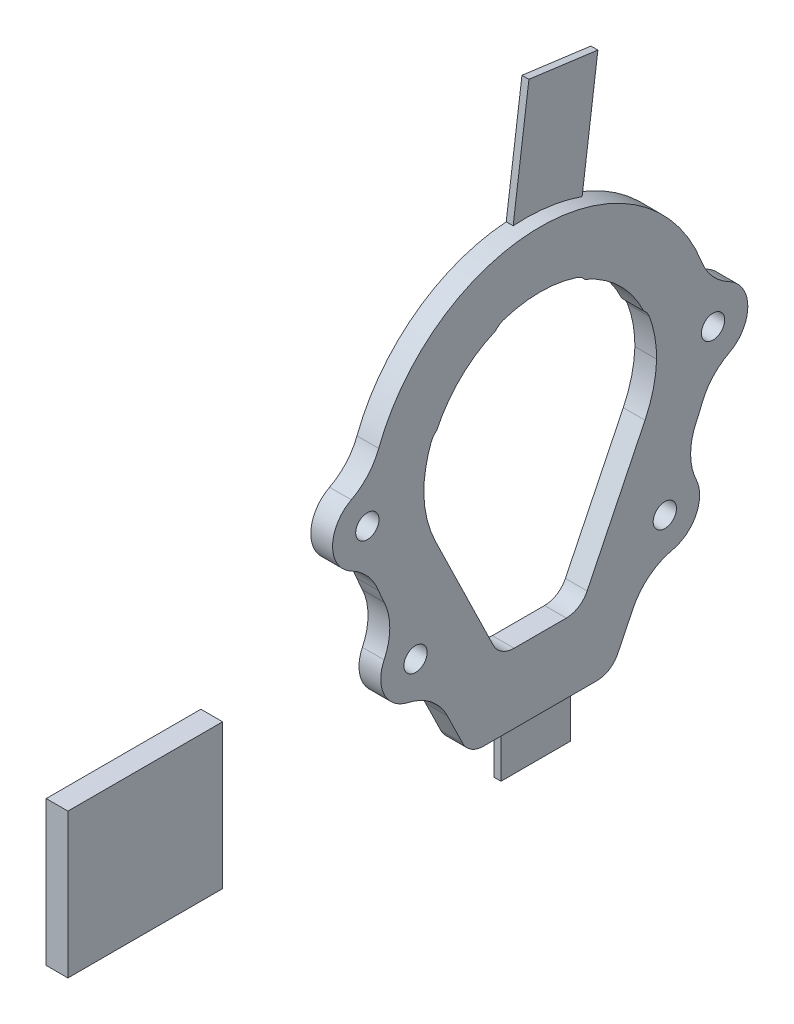
SolidWorks part; units mm, degrees
material "6061-T6 (SS)"
ref_plane "Front Plane" through (0, 0, 0) normal (0, 0, 1) x (1, 0, 0)
ref_plane "Top Plane" through (0, 0, 0) normal (0, 1, 0) x (1, 0, 0)
ref_plane "Right Plane" through (0, 0, 0) normal (1, 0, 0) x (0, 0, -1)
sketch "Sketch1" plane through (0, 0, 0) normal (1, 0, 0) x (0, 0, -1)
  line L0 (25.508, 0) -> (25.508, -5.08)
  line L1 (-25.508, 0) -> (-25.508, -5.08)
  line L2 (0, 0) -> (-22.6577, 10.5655) construction
  line L3 (0, 0) -> (-9.7683, 23.0126) construction
  line L4 (0, 0) -> (-25.508, 0) construction
  line L5 (-5.715, -39.224) -> (5.715, -39.224)
  line L6 (10.2829, -36.3669) -> (25.508, -5.08)
  line L7 (-10.2829, -36.3669) -> (-25.508, -5.08)
  line L8 (-15.6001, -54.464) -> (15.6001, -54.464)
  line L9 (15.6001, -54.464) -> (34.0424, -16.5661)
  line L10 (-34.0424, -16.5661) -> (-15.6001, -54.464)
  line L11 (25.508, -5.08) -> (36.9276, -10.6371) construction
  line L12 (-25.508, -5.08) -> (-36.9276, -10.6371) construction
  arc A0 (-9.7683, 23.0126) -> (-22.6577, 10.5655) centre (0, 0) ccw
  arc A1 (25.508, 0) -> (23.9202, 8.8591) centre (0, 0) ccw
  arc A2 (-9.7683, 23.0126) -> (-8.0189, 24.2148) centre (-6.8212, 20.5979) cw
  arc A3 (9.7683, 23.0126) -> (8.0189, 24.2148) centre (6.8212, 20.5979) ccw
  arc A4 (22.6577, 10.5655) -> (23.9202, 8.8591) centre (20.3473, 7.5359) cw
  arc A5 (-23.9202, 8.8591) -> (-22.6577, 10.5655) centre (-20.3473, 7.5359) cw
  arc A6 (22.6577, 10.5655) -> (9.7683, 23.0126) centre (0, 0) ccw
  arc A7 (-23.9202, 8.8591) -> (-25.508, 0) centre (0, 0) ccw
  arc A8 (8.0189, 24.2148) -> (-8.0189, 24.2148) centre (0, 0) ccw
  circle A9 centre (0, 0) radius 25 construction
  arc A10 (5.715, -39.224) -> (10.2829, -36.3669) centre (5.715, -34.144) ccw
  arc A11 (-5.715, -39.224) -> (-10.2829, -36.3669) centre (-5.715, -34.144) cw
  arc A12 (34.0424, -16.5661) -> (-34.0424, -16.5661) centre (0, 0) ccw
  point P25 (0, -39.224)
  dimension "D1" = 50
  dimension "D2" = 0.508
  dimension "D3" = 3.81
  dimension "D4" = 25
  dimension "D6" = 14.224
  dimension "D7" = 11.43
  dimension "D8" = 5.08
  dimension "D10" = 12.7
  dimension "D5" = 67
  dimension "D9" = 5.08
  dimension "D11" = 15.24
extrude "Boss-Extrude1" add sketch "Sketch1" along normal blind 4.7625
fillet "Fillet1" radius 25.4 2 edges at (2.3813, -5.08, 25.508) (2.3813, -5.08, -25.508)
fillet "Fillet2" radius 5.08 2 edges at (2.3813, -54.464, 15.6001) (2.3813, -54.464, -15.6001)
sketch "Sketch2" plane through (4.7625, 0, 0) normal (1, 0, 0) x (0, 0, -1)
  line L0 (-37.8592, 0) -> (37.8592, 0) construction
  line L1 (27.305, -30.48) -> (-27.305, -30.48) construction
  line L2 (0, 0) -> (0, -30.48) construction
  circle A0 centre (37.8592, 0) radius 7.62
  circle A1 centre (-37.8592, 0) radius 7.62
  circle A2 centre (-27.305, -30.48) radius 7.62
  circle A3 centre (27.305, -30.48) radius 7.62
  arc A5 (34.0424, -16.5661) -> (-34.0424, -16.5661) centre (0, 0) ccw construction
  dimension "D1" = 15.24
  dimension "D3" = 54.61
  dimension "D2" = 0
  dimension "D4" = 30.48
extrude "Boss-Extrude2" add sketch "Sketch2" against normal through all
fillet "Fillet3" radius 12.7 8 edges at (2.3813, 7.5813, -37.0924) (2.3813, 7.5813, 37.0924) (2.3813, -7.5813, -37.0924) (2.3813, -7.5813, 37.0924) (2.3813, -37.3185, -23.9436) (2.3813, -23.6151, -30.6122) (2.3813, -37.3185, 23.9436) (2.3813, -23.6151, 30.6122)
hole_wizard "#10 Clearance Hole1" positions "Sketch4" profile "Sketch5" hole size "#10" standard "ANSI Inch" end condition through all
sketch "Sketch4" plane through (4.7625, 0, 0) normal (1, 0, 0) x (0, 0, -1)
  arc A0 (-34.1836, -27.2014) -> (-28.9704, -37.9158) centre (-27.305, -30.48) ccw construction
  arc A1 (28.9704, -37.9158) -> (34.1836, -27.2014) centre (27.305, -30.48) ccw construction
  point P0 (-37.8592, 0)
  point P3 (37.8592, 0)
  point P6 (27.305, -30.48)
  point P8 (-27.305, -30.48)
sketch "Sketch5" plane through (4.7625, 0, 37.8592) normal (0, 1, 0) x (0, 0, -1)
  line L0 (0, 0) -> (0, 4.7625)
  line L1 (0, 4.7625) -> (2.5527, 4.7625)
  line L2 (2.5527, 4.7625) -> (2.5527, 0)
  line L5 (2.5527, 0) -> (0, 0)
  line L11 (0, -6.35) -> (0, 107.95) construction
  dimension "Thru Hole Dia." = 5.1054
  dimension "Thru Hole Depth" = 4.7625
sketch "Sketch6" plane through (4.7625, 0, 0) normal (1, 0, 0) x (0, 0, -1)
  line L1 (-69.5589, -52.9167) -> (-103.449, -52.9167)
  line L2 (-69.5589, -52.9167) -> (-69.5589, -21.2552)
  line L3 (-69.5589, -21.2552) -> (-103.449, -21.2552)
  line L4 (-103.449, -52.9167) -> (-103.449, -21.2552)
  line L5 (-69.5589, -52.9167) -> (-103.449, -21.2552) construction
  line L6 (-69.5589, -21.2552) -> (-103.449, -52.9167) construction
  point P4 (-86.5039, -37.086)
extrude "Boss-Extrude3" add sketch "Sketch6" against normal up to surface (4.7625 mm away) separate body up to face at (0, 0, 35.3065)
sketch "Sketch7" plane through (0, 0, 0) normal (-1, 0, 0) x (0, 0, 1)
  line L0 (5.3499, -54.464) -> (-9.8901, -54.464)
  line L1 (5.3499, -54.464) -> (5.3499, -66.2754)
  line L2 (-9.8901, -54.464) -> (-9.8901, -66.2754)
  line L3 (5.3499, -66.2754) -> (-9.8901, -66.2754)
  line L4 (12.4227, -54.464) -> (-12.4227, -54.464) construction
  line L5 (-12.4227, 35.7631) -> (2.6854, 37.7639)
  line L6 (-12.4227, 35.7631) -> (-15.8752, 61.8336)
  line L7 (2.6854, 37.7639) -> (-0.7671, 63.8344)
  line L8 (-15.8752, 61.8336) -> (-0.7671, 63.8344)
  arc A0 (35.371, 13.4988) -> (-35.371, 13.4988) centre (0, 0) ccw construction
  dimension "D1" = 15.24
extrude "Boss-Extrude4" add sketch "Sketch7" against normal blind 1.524
